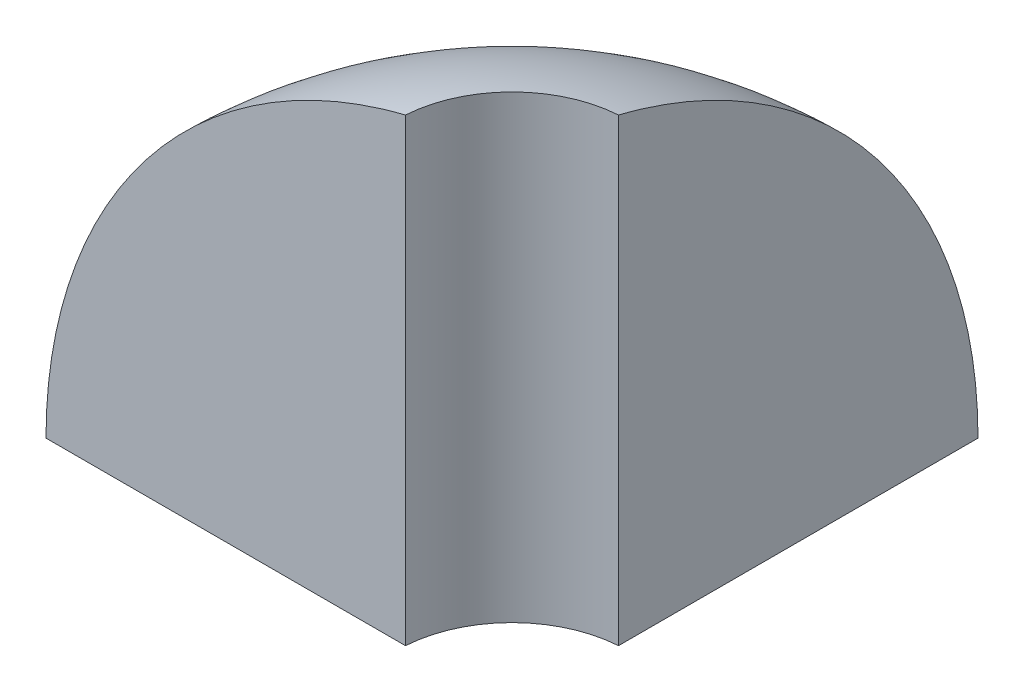
SolidWorks part; units mm, degrees
ref_plane "Front Plane" through (0, 0, 0) normal (0, 0, 1) x (1, 0, 0)
ref_plane "Top Plane" through (0, 0, 0) normal (0, 1, 0) x (1, 0, 0)
ref_plane "Right Plane" through (0, 0, 0) normal (1, 0, 0) x (0, 0, -1)
sketch "Sketch1" plane through (0, 0, 0) normal (0, 0, 1) x (1, 0, 0)
  line L0 (0, 31.5) -> (0, -31.5)
  arc A0 (0, 31.5) -> (0, -31.5) centre (0, 0) ccw
  dimension "D1" = 31.5
revolve "Revolve1" add sketch "Sketch1" angle 360 about L0
sketch "Sketch2" plane through (0, 0, 0) normal (0, 1, 0) x (1, 0, 0)
  line L0 (0, 16.8) -> (0, 0) construction
  line L1 (0, 0) -> (-16.8, 0) construction
  line L2 (-0.5, 31.496) -> (-0.5, 0.5)
  line L3 (-0.5, 0.5) -> (-31.496, 0.5)
  arc A2 (-31.496, 0.5) -> (-0.5, 31.496) centre (0, 0) ccw
  circle A3 centre (0, 0) radius 31.5 construction
  dimension "D1" = 0.5
  dimension "D2" = 0.5
extrude "Cut-Extrude1" cut sketch "Sketch2" against normal through all both and the other way through all
sketch "Sketch3" plane through (-0.5, 0, 0) normal (1, 0, 0) x (0, 0, -1)
  line L1 (0, 0) -> (31.496, 0)
  line L2 (0, 0) -> (0, -31.496)
  line L3 (0, -31.496) -> (31.496, -31.496)
  line L4 (31.496, 0) -> (31.496, -31.496)
  arc A0 (0.5, -31.4921) -> (0.5, 31.4921) centre (0, 0) ccw construction
extrude "Cut-Extrude2" cut sketch "Sketch3" against normal through all
sketch "Sketch6" plane through (0, 0, 0) normal (0, -1, 0) x (1, 0, 0)
  circle A0 centre (0, 0) radius 7.6
  dimension "D1" = 15.2
extrude "Cut-Extrude3" cut sketch "Sketch6" against normal through all
